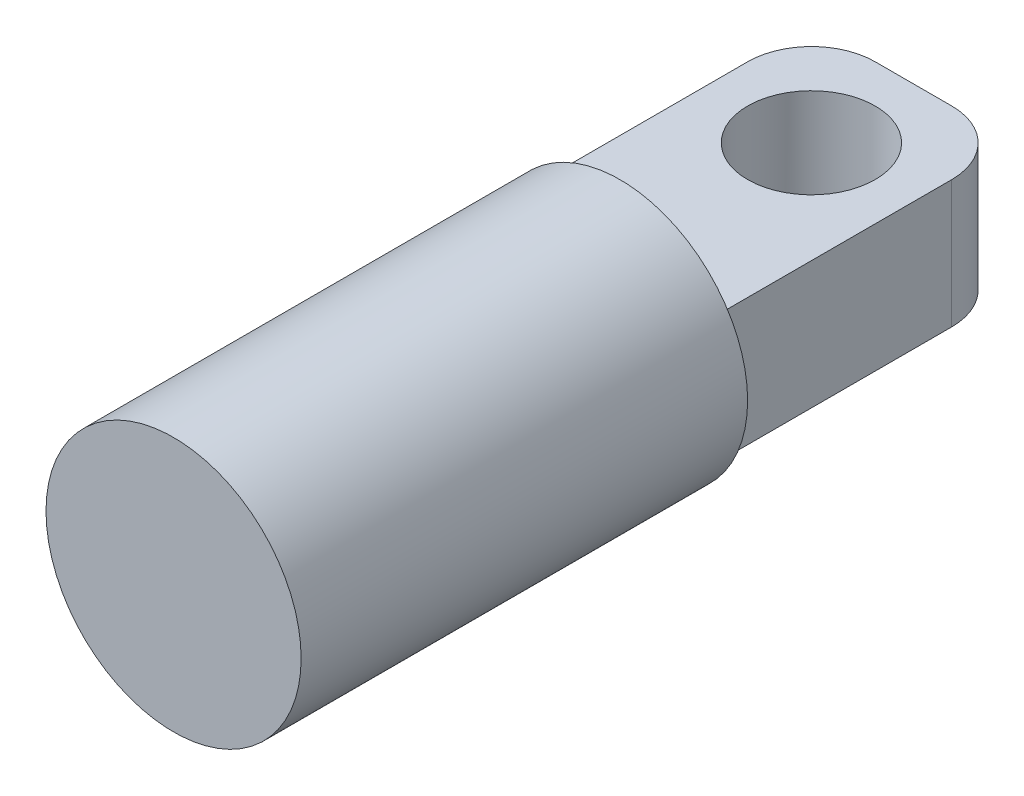
SolidWorks part; units mm, degrees
ref_plane "Front Plane" through (0, 0, 0) normal (0, 0, 1) x (1, 0, 0)
ref_plane "Top Plane" through (0, 0, 0) normal (0, 1, 0) x (1, 0, 0)
ref_plane "Right Plane" through (0, 0, 0) normal (1, 0, 0) x (0, 0, -1)
sketch "Sketch1" plane through (0, 0, 0) normal (0, 0, 1) x (1, 0, 0)
  circle A0 centre (0, 0) radius 25.4
extrude "Boss-Extrude1" add sketch "Sketch1" against normal blind 88.9
sketch "Sketch2" plane through (0, 0, 0) normal (1, 0, 0) x (0, 0, -1)
  line L0 (88.9, -25.4) -> (88.9, 25.4) construction
  line L1 (88.9, -25.4) -> (88.9, 25.4)
  line L3 (88.9, -12.7) -> (147.32, -12.7)
  line L4 (88.9, -12.7) -> (88.9, 12.7)
  line L5 (88.9, 12.7) -> (147.32, 12.7)
  line L6 (147.32, -12.7) -> (147.32, 12.7)
  dimension "D1" = 25.4
  dimension "D2" = 12.7
  dimension "D3" = 58.42
extrude "Boss-Extrude2" add sketch "Sketch2" along normal blind 20.32 and the other way blind 20.32 contours L3 L6 L5 L1 region at (0, 0, -118.11)
fillet "Fillet1" radius 12.7 2 edges at (20.32, 0, -147.32) (-20.32, 0, -147.32)
sketch "Sketch3" plane through (0, 12.7, 0) normal (0, 1, 0) x (1, 0, 0)
  line L4 (20.32, 88.9) -> (20.32, 134.62)
  line L5 (7.62, 147.32) -> (-7.62, 147.32)
  line L6 (-20.32, 134.62) -> (-20.32, 88.9)
  line L7 (-20.32, 88.9) -> (20.32, 88.9)
  line L8 (20.32, 88.9) -> (20.32, 134.62)
  line L9 (7.62, 147.32) -> (-7.62, 147.32)
  line L10 (-20.32, 134.62) -> (-20.32, 88.9)
  line L11 (-20.32, 88.9) -> (20.32, 88.9)
  circle A0 centre (0, 127) radius 12.7
  arc A2 (20.32, 134.62) -> (7.62, 147.32) centre (7.62, 134.62) ccw
  arc A3 (-7.62, 147.32) -> (-20.32, 134.62) centre (-7.62, 134.62) ccw
  arc A4 (20.32, 134.62) -> (7.62, 147.32) centre (7.62, 134.62) ccw
  arc A5 (-7.62, 147.32) -> (-20.32, 134.62) centre (-7.62, 134.62) ccw
  dimension "D2" = 127
  dimension "D3" = 25.4
  dimension "D4" = 20.32
  dimension "D1" = 0
extrude "Cut-Extrude3" cut sketch "Sketch3" against normal through all contours A0
